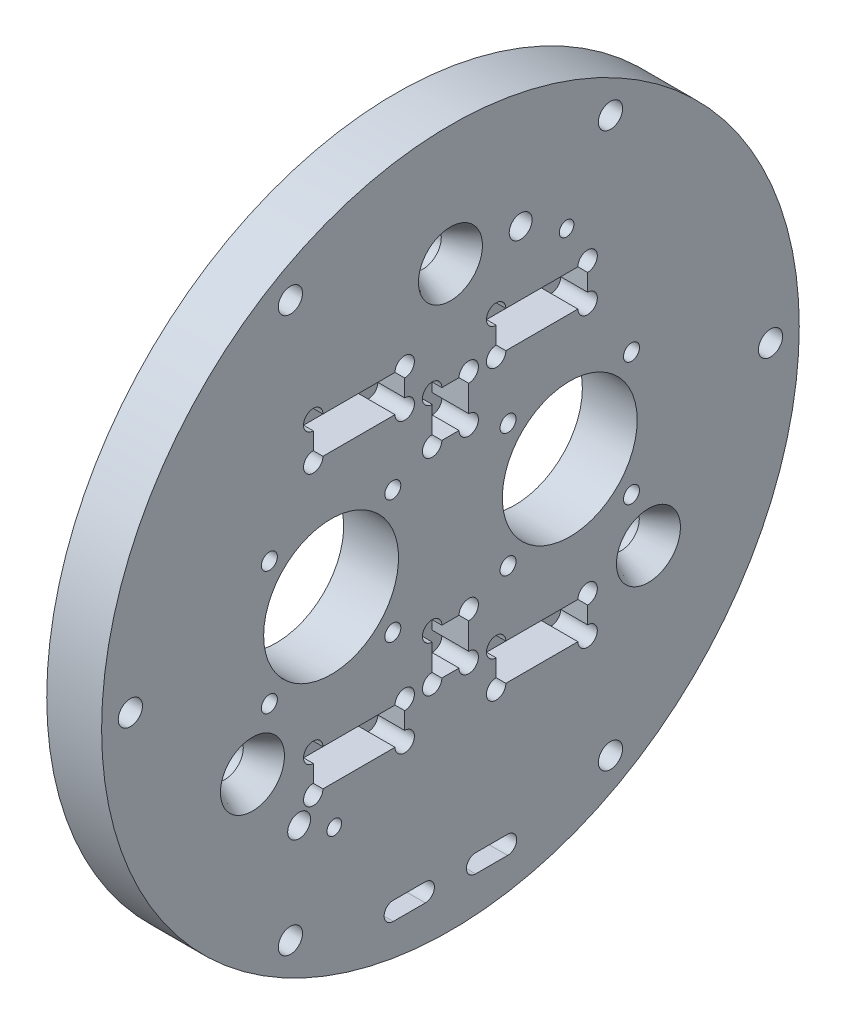
SolidWorks part; units mm, degrees
ref_plane "Front Plane" through (0, 0, 0) normal (0, 0, 1) x (1, 0, 0)
ref_plane "Top Plane" through (0, 0, 0) normal (0, 1, 0) x (1, 0, 0)
ref_plane "Right Plane" through (0, 0, 0) normal (1, 0, 0) x (0, 0, -1)
sketch "Sketch1" plane through (0, 0, 0) normal (1, 0, 0) x (0, 0, -1)
  line L0 (0, -76.29) -> (0, 76.29) construction
  line L1 (-76.29, 0) -> (76.29, 0) construction
  line L2 (26.1, 0) -> (39.5969, 13.4969) construction
  circle A0 centre (0, 0) radius 76.29
  circle A1 centre (0, 50) radius 4
  circle A2 centre (43.3013, -25) radius 4
  circle A3 centre (-43.3013, -25) radius 4
  circle A4 centre (26.1, 0) radius 14.75
  circle A5 centre (-26.1, 0) radius 14.75
  circle A6 centre (39.5969, 13.4969) radius 1.75
  circle A7 centre (39.5969, -13.4969) radius 1.75
  circle A8 centre (12.6031, -13.4969) radius 1.75
  circle A9 centre (12.6031, 13.4969) radius 1.75
  circle A10 centre (-39.5969, -13.4969) radius 1.75
  circle A11 centre (-12.6031, -13.4969) radius 1.75
  circle A12 centre (-12.6031, 13.4969) radius 1.75
  circle A13 centre (-39.5969, 13.4969) radius 1.75
  circle A14 centre (26.1, 0) radius 22.1 construction
  circle A15 centre (-26.1, 0) radius 22.1 construction
  circle A16 centre (-22.3739, -41.5) radius 2.5 construction
  point P12 (0, 0)
  point P29 (26.1, 0)
  point P37 (-4, 0)
  point P40 (4, 0)
  dimension "D1" = 152.58
  dimension "D2" = 8
  dimension "D5" = 29.5
  dimension "D7" = 3.5
  dimension "D11" = 44.2
  dimension "D3" = 50
  dimension "D4" = 3
  dimension "D6" = 8
  dimension "D8" = 19.0875
  dimension "D10" = 45
  dimension "D9" = 4
extrude "Boss-Extrude1" add sketch "Sketch1" along normal blind 12
sketch "Sketch2" plane through (12, 0, 0) normal (1, 0, 0) x (0, 0, -1)
  line L0 (-97.5918, 0) -> (102.3086, 0) construction
  line L1 (0, 96.3466) -> (0, -103.9448) construction
  line L2 (10, -27.5) -> (10, -35.5)
  line L3 (-30, -27.5) -> (-10, -27.5)
  line L4 (-30, -27.5) -> (-30, -35.5)
  line L5 (-30, -35.5) -> (-10, -35.5)
  line L6 (-10, -27.5) -> (-10, -35.5)
  line L7 (30, -27.5) -> (10, -27.5)
  line L8 (30, -27.5) -> (30, -35.5)
  line L9 (30, -35.5) -> (10, -35.5)
  line L10 (-30, 27.5) -> (-30, 35.5)
  line L11 (-30, 35.5) -> (-10, 35.5)
  line L12 (-10, 27.5) -> (-10, 35.5)
  line L13 (-30, 27.5) -> (-10, 27.5)
  line L14 (10, 27.5) -> (10, 35.5)
  line L15 (30, 35.5) -> (10, 35.5)
  line L16 (30, 27.5) -> (10, 27.5)
  line L17 (30, 27.5) -> (30, 35.5)
  line L18 (-4, -17.5) -> (4, -17.5)
  line L19 (-4, 27.5) -> (4, 27.5)
  line L20 (-4, 27.5) -> (-4, 17.5)
  line L21 (-4, 17.5) -> (4, 17.5)
  line L22 (4, 27.5) -> (4, 17.5)
  line L23 (-4, -27.5) -> (-4, -17.5)
  line L24 (-4, -27.5) -> (4, -27.5)
  line L25 (4, -27.5) -> (4, -17.5)
  line L26 (27.8787, -35.5) -> (30, -33.3787) construction
  line L27 (-42.3534, -68.29) -> (39.6493, -68.29) construction
  line L28 (-5.5, -68.29) -> (-5.5, -64.29)
  line L29 (12.5, -68.29) -> (5.5, -68.29)
  line L30 (12.5, -68.29) -> (12.5, -64.29)
  line L31 (12.5, -64.29) -> (5.5, -64.29)
  line L32 (5.5, -68.29) -> (5.5, -64.29)
  line L33 (-12.5, -64.29) -> (-5.5, -64.29)
  line L34 (-12.5, -68.29) -> (-12.5, -64.29)
  line L35 (-12.5, -68.29) -> (-5.5, -68.29)
  circle A0 centre (30, -35.5) radius 2.1213 construction
  circle A1 centre (0, 0) radius 76.29 construction
  point P23 (0, 27.5)
  point P31 (30, -33.3787)
  point P32 (0, -76.29)
  point P33 (27.8787, -35.5)
  dimension "D1" = 27.5
  dimension "D2" = 8
  dimension "D3" = 20
  dimension "D4" = 20
  dimension "D5" = 8
  dimension "D6" = 10
  dimension "D7" = 8
  dimension "D8" = 4
  dimension "D9" = 7
  dimension "D10" = 25
extrude "Cut-Extrude1" cut sketch "Sketch2" against normal blind 8
sketch "Sketch3" plane through (0, 0, 0) normal (-1, 0, 0) x (0, 0, 1)
  circle A0 centre (-70, 0) radius 2.65
  circle A1 centre (-35, 60.6218) radius 2.65
  circle A2 centre (35, 60.6218) radius 2.65
  circle A3 centre (70, 0) radius 2.65
  circle A4 centre (35, -60.6218) radius 2.65
  circle A5 centre (-35, -60.6218) radius 2.65
  point P16 (0, 0)
  dimension "D2" = 5.3
  dimension "D1" = 70
  dimension "D3" = 6
extrude "Cut-Extrude2" cut sketch "Sketch3" against normal up to next
sketch "Sketch4" plane through (12, 0, 0) normal (1, 0, 0) x (0, 0, -1)
  line L0 (12.5, -68.29) -> (12.5, -64.29) construction
  line L2 (5.5, -64.29) -> (5.5, -68.29) construction
  line L3 (-5.5, -68.29) -> (-5.5, -64.29) construction
  line L4 (-12.5, -64.29) -> (-12.5, -68.29) construction
  circle A0 centre (-10, -35.5) radius 2.1213
  circle A1 centre (-10, -27.5) radius 2.1213
  circle A2 centre (-30, -27.5) radius 2.1213
  circle A3 centre (-30, -35.5) radius 2.1213
  circle A4 centre (12.5, -66.29) radius 2
  circle A5 centre (5.5, -66.29) radius 2
  circle A6 centre (-5.5, -66.29) radius 2
  circle A7 centre (-12.5, -66.29) radius 2
  circle A12 centre (10, -35.5) radius 2.1213
  circle A13 centre (10, -27.5) radius 2.1213
  circle A14 centre (30, -27.5) radius 2.1213
  circle A15 centre (30, -35.5) radius 2.1213
  circle A16 centre (4, -27.5) radius 2.1213
  circle A17 centre (-4, -27.5) radius 2.1213
  circle A18 centre (-4, -17.5) radius 2.1213
  circle A19 centre (4, -17.5) radius 2.1213
  circle A20 centre (4, 27.5) radius 2.1213
  circle A21 centre (-4, 27.5) radius 2.1213
  circle A22 centre (-4, 17.5) radius 2.1213
  circle A23 centre (4, 17.5) radius 2.1213
  circle A24 centre (10, 27.5) radius 2.1213
  circle A25 centre (10, 35.5) radius 2.1213
  circle A26 centre (30, 35.5) radius 2.1213
  circle A27 centre (30, 27.5) radius 2.1213
  circle A28 centre (-10, 35.5) radius 2.1213
  circle A29 centre (-10, 27.5) radius 2.1213
  circle A30 centre (-30, 27.5) radius 2.1213
  circle A31 centre (-30, 35.5) radius 2.1213
  point P2 (-12.1213, -35.5)
  point P5 (-10, -33.3787)
  dimension "D1" = 3
extrude "Cut-Extrude3" cut sketch "Sketch4" against normal up to surface (8 mm away) up to face at (4, -31.5, 20)
sketch "Sketch5" plane through (0, 0, 0) normal (-1, 0, 0) x (0, 0, 1)
  line L0 (35, -60.6218) -> (-35, 60.6218) construction
  line L1 (0, 113.7201) -> (0, -122.5246) construction
  line L2 (-128.5049, 0) -> (121.7105, 0) construction
  circle A0 centre (35, -60.6218) radius 2.65 construction
  circle A1 centre (25.4034, -44) radius 1.6
  circle A2 centre (-25.4034, 44) radius 1.6
  point P12 (0, 0)
  dimension "D2" = 3.2
  dimension "D1" = 2
  dimension "D3" = 44
  dimension "D4" = 50.8068
extrude "Cut-Extrude4" cut sketch "Sketch5" against normal up to next
sketch "Sketch9" plane through (12, 0, 0) normal (1, 0, 0) x (0, 0, -1)
  circle A0 centre (0, 0) radius 51.7766 construction
  circle A1 centre (0, 51.7766) radius 15.533 construction
  circle A2 centre (15.3572, 49.4467) radius 2.5
  circle A4 centre (-33.0898, -39.8231) radius 2.5
  circle A5 centre (-43.3013, -25) radius 4 construction
  dimension "D1" = 5
  dimension "D2" = 5
  dimension "D3" = 18
extrude "Cut-Extrude6" cut sketch "Sketch9" against normal up to next
chamfer "Chamfer1" distance 3 distance2 6 3 edges at (12, 50, -4) (12, -25, -47.3013) (12, -25, 39.3013) first distance on face at (12, -39.8231, 30.5898)
